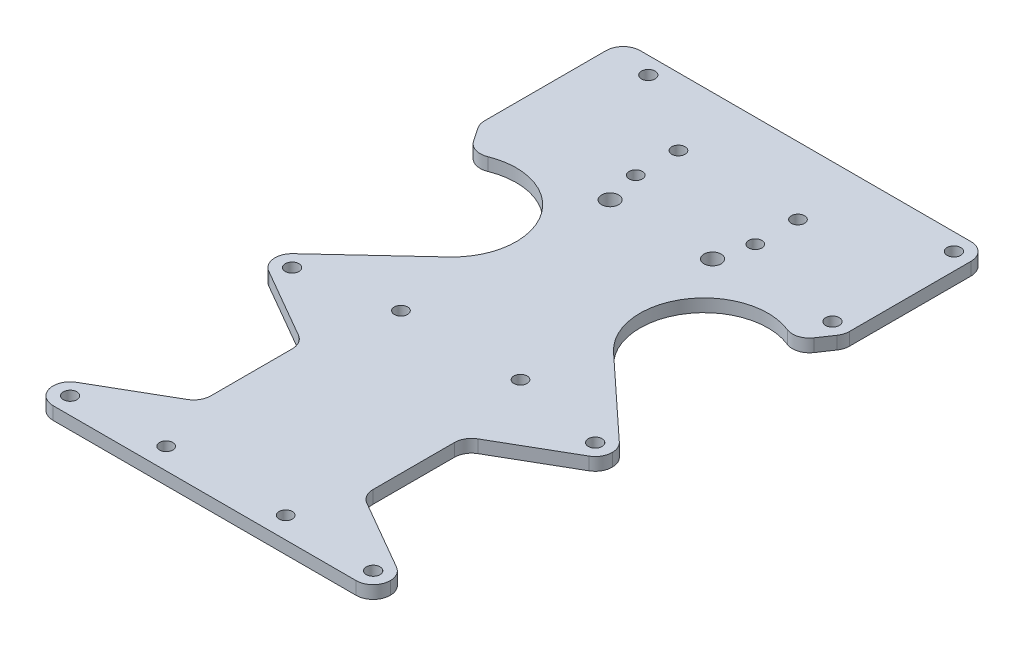
SolidWorks part; units mm, degrees
material "Thornel Mat VMA"
ref_plane "Front Plane" through (0, 0, 0) normal (0, 0, 1) x (1, 0, 0)
ref_plane "Top Plane" through (0, 0, 0) normal (0, 1, 0) x (1, 0, 0)
ref_plane "Right Plane" through (0, 0, 0) normal (1, 0, 0) x (0, 0, -1)
sketch "Sketch1" plane through (0, 0, 0) normal (0, 1, 0) x (1, 0, 0)
  line L0 (0, 0) -> (0, -82.5) construction
  line L1 (29.5, 0) -> (0, 0) construction
  line L19 (14, -27.5) -> (-14, -27.5) construction
  line L22 (14, -27.5) -> (14, 27.5) construction
  line L25 (14, 27.5) -> (-14, 27.5) construction
  line L28 (-14, -27.5) -> (-14, 27.5) construction
  line L38 (14, -27.5) -> (-14, 27.5) construction
  line L41 (47.5, 62.5) -> (-47.5, 62.5)
  line L44 (47.5, 62.5) -> (47.5, -87.5)
  line L47 (47.5, -87.5) -> (-47.5, -87.5)
  line L50 (-47.5, 62.5) -> (-47.5, -87.5)
  line L59 (-959, -57) -> (49041, -57) construction
  line L65 (14, 27.5) -> (-14, -27.5) construction
  line L66 (-14, 37.5) -> (14, 37.5) construction
  line L67 (-14, 37.5) -> (-14, 27.5) construction
  line L69 (14, 37.5) -> (14, 27.5) construction
  line L74 (-14, -27.5) -> (-14, -82.5) construction
  line L75 (-14, -82.5) -> (14, -82.5) construction
  line L76 (14, -82.5) -> (14, -27.5) construction
  line L94 (0, -82.5) -> (0, -87.5) construction
  circle A0 centre (29.5, 0) radius 15
  circle A22 centre (14, 27.5) radius 1.55
  circle A23 centre (14, -27.5) radius 1.55
  circle A24 centre (-14, -27.5) radius 1.55
  circle A25 centre (-14, 27.5) radius 1.55
  circle A76 centre (-14, 37.5) radius 1.55
  circle A77 centre (14, 37.5) radius 1.55
  circle A91 centre (-14, -82.5) radius 1.55
  circle A92 centre (14, -82.5) radius 1.55
  circle A99 centre (-29.5, 0) radius 15
  point P1 (0, -53.5)
  point P37 (29.5, 0)
  point P51 (0, 32.5)
  dimension "D1" = 30
  dimension "D6" = 25
  dimension "D7" = 5
  dimension "D10" = 3.1
  dimension "D12" = 55
  dimension "D15" = 10
  dimension "D19" = 28
  dimension "D20" = 29.5
  dimension "D3" = 95
  dimension "D14" = 55
extrude "凸台-拉伸1" add sketch "Sketch1" along normal blind 3 contours L41 L50 L47 L44 A23 A22 A0 region at (0, 0, 13.8891)
sketch "草图9" plane through (0, 0, 0) normal (0, 1, 0) x (1, 0, 0)
  line L0 (0, 35) -> (0, 0) construction
  line L1 (42.55, 7.5) -> (-42.55, 7.5) construction
  line L2 (42.55, 7.5) -> (42.55, 62.5) construction
  line L3 (42.55, 62.5) -> (-42.55, 62.5) construction
  line L4 (-42.55, 7.5) -> (-42.55, 62.5) construction
  line L5 (42.55, 7.5) -> (-42.55, 62.5) construction
  line L6 (42.55, 62.5) -> (-42.55, 7.5) construction
  line L7 (-32.84, 49.29) -> (38.74, 49.29) construction
  line L8 (38.74, 49.29) -> (38.74, 20.84) construction
  circle A0 centre (-14, 27.5) radius 1.55 construction
  circle A1 centre (38.74, 20.84) radius 1.6
  circle A2 centre (38.74, 49.29) radius 1.6
  circle A3 centre (-32.84, 49.29) radius 1.6
  point P0 (0, 35)
  dimension "D6" = 3.2
  dimension "D1" = 55
  dimension "D2" = 85.1
  dimension "D3" = 20
  dimension "D4" = 3.81
  dimension "D5" = 13.21
  dimension "D7" = 13.34
  dimension "D8" = 9.71
extrude "主控板固定孔" cut sketch "草图9" along normal up to next
sketch "草图10" plane through (0, 0, 0) normal (0, 1, 0) x (1, 0, 0)
  line L0 (0, 0) -> (0, -57.5) construction
  line L1 (35.5, -83.5) -> (-35.5, -83.5) construction
  line L2 (35.5, -83.5) -> (35.5, -31.5) construction
  line L3 (35.5, -31.5) -> (-35.5, -31.5) construction
  line L4 (-35.5, -83.5) -> (-35.5, -31.5) construction
  line L5 (35.5, -83.5) -> (-35.5, -31.5) construction
  line L6 (35.5, -31.5) -> (-35.5, -83.5) construction
  line L7 (47.5, -87.5) -> (-47.5, -87.5) construction
  circle A0 centre (35.5, -31.5) radius 1.6
  circle A1 centre (35.5, -83.5) radius 1.6
  circle A2 centre (-35.5, -31.5) radius 1.6
  circle A3 centre (-35.5, -83.5) radius 1.6
  point P0 (0, -57.5)
  dimension "D1" = 4
  dimension "D2" = 3.2
  dimension "D3" = 52
  dimension "D4" = 71
extrude "图传固定孔" cut sketch "草图10" along normal up to next
sketch "草图11" plane through (0, 0, 0) normal (0, 1, 0) x (1, 0, 0)
  line L0 (0, 0) -> (0, 22.5) construction
  line L1 (9, -22.5) -> (-9, -22.5) construction
  line L2 (9, -22.5) -> (9, 22.5) construction
  line L3 (9, 22.5) -> (-9, 22.5) construction
  line L4 (-9, -22.5) -> (-9, 22.5) construction
  line L5 (9, -22.5) -> (-9, 22.5) construction
  line L6 (9, 22.5) -> (-9, -22.5) construction
  circle A0 centre (-29.5, 0) radius 22.5 construction
  circle A1 centre (-14, 27.5) radius 1.55 construction
  circle A2 centre (-12, 19.5) radius 2
  circle A3 centre (12, 19.5) radius 2
  point P3 (0, 0)
  dimension "D1" = 45
  dimension "D4" = 4
  dimension "D2" = 18
  dimension "D3" = 5
  dimension "D5" = 3
  dimension "D6" = 3
extrude "光电二极管留孔" cut sketch "草图11" along normal up to next
sketch "草图8" plane through (0, 0, 0) normal (0, 1, 0) x (1, 0, 0)
  line L3 (47.5, 62.5) -> (47.5, -87.5)
  line L13 (0, 62.5) -> (0, -87.5) construction
  line L14 (0, 62.5) -> (0, 53.29)
  line L15 (47.5, 62.5) -> (-47.5, 62.5) construction
  line L16 (47.5, -87.5) -> (-47.5, -87.5) construction
  line L17 (0, 62.5) -> (47.5, 62.5)
  line L18 (0, 53.29) -> (42.74, 53.29)
  line L20 (42.74, 53.29) -> (42.74, 19.6164)
  line L23 (39.5, -29.7557) -> (39.5, -33.8094)
  line L27 (47.5, -87.5) -> (39.5, -87.5)
  line L28 (42.74, 19.6164) -> (29.5, 0)
  line L32 (19.2931, -10.9918) -> (39.5, -29.7557)
  line L37 (39.5, -33.8094) -> (19, -45.6451)
  line L38 (19, -45.6451) -> (19, -69.3549)
  line L39 (19, -69.3549) -> (39.5, -81.1906)
  line L40 (19, -57.5) -> (-1.5333, -57.5) construction
  line L41 (-1.5333, -57.5) -> (19, -45.6451) construction
  line L42 (19, -69.3549) -> (-1.5333, -57.5) construction
  line L43 (39.5, -81.1906) -> (39.5, -87.5)
  line L44 (29.5, 0) -> (19.2931, -10.9918)
  circle A0 centre (14, -82.5) radius 1.55 construction
  circle A2 centre (38.74, 49.29) radius 1.6 construction
  circle A3 centre (38.74, 20.84) radius 1.6 construction
  circle A4 centre (29.5, 0) radius 15 construction
  circle A5 centre (35.5, -83.5) radius 1.6 construction
  circle A6 centre (35.5, -31.5) radius 1.6 construction
  dimension "D1" = 4
  dimension "D2" = 4
  dimension "D3" = 4
  dimension "D4" = 4
  dimension "D6" = 4
  dimension "D7" = 5
  dimension "D5" = 4
  dimension "D8" = 60
  dimension "D9" = 4
extrude "板型" cut sketch "草图8" along normal up to next contours L17 L3 L27 L43 L39 L38 L37 L23 L32 L44 L28 L20 L18 L14
mirror "镜向1" about plane through (0, 0, 0) normal (1, 0, 0) of "板型"
fillet "圆角1" radius 4 18 edges at (-39.5, 1.5, 29.7557) (-37.8916, 1.5, -12.433) (-42.74, 1.5, -19.6164) (-42.74, 1.5, -53.29) (42.74, 1.5, -53.29) (42.74, 1.5, -19.6164) (37.8916, 1.5, -12.433) (39.5, 1.5, 29.7557) (-39.5, 1.5, 81.1906) (-19, 1.5, 69.3549) (-19, 1.5, 45.6451) (-39.5, 1.5, 33.8094) (39.5, 1.5, 33.8094) (19, 1.5, 45.6451) (19, 1.5, 69.3549) (39.5, 1.5, 81.1906) (39.5, 1.5, 87.5) (-39.5, 1.5, 87.5)
fillet "圆角2" [suppressed] radius 5
